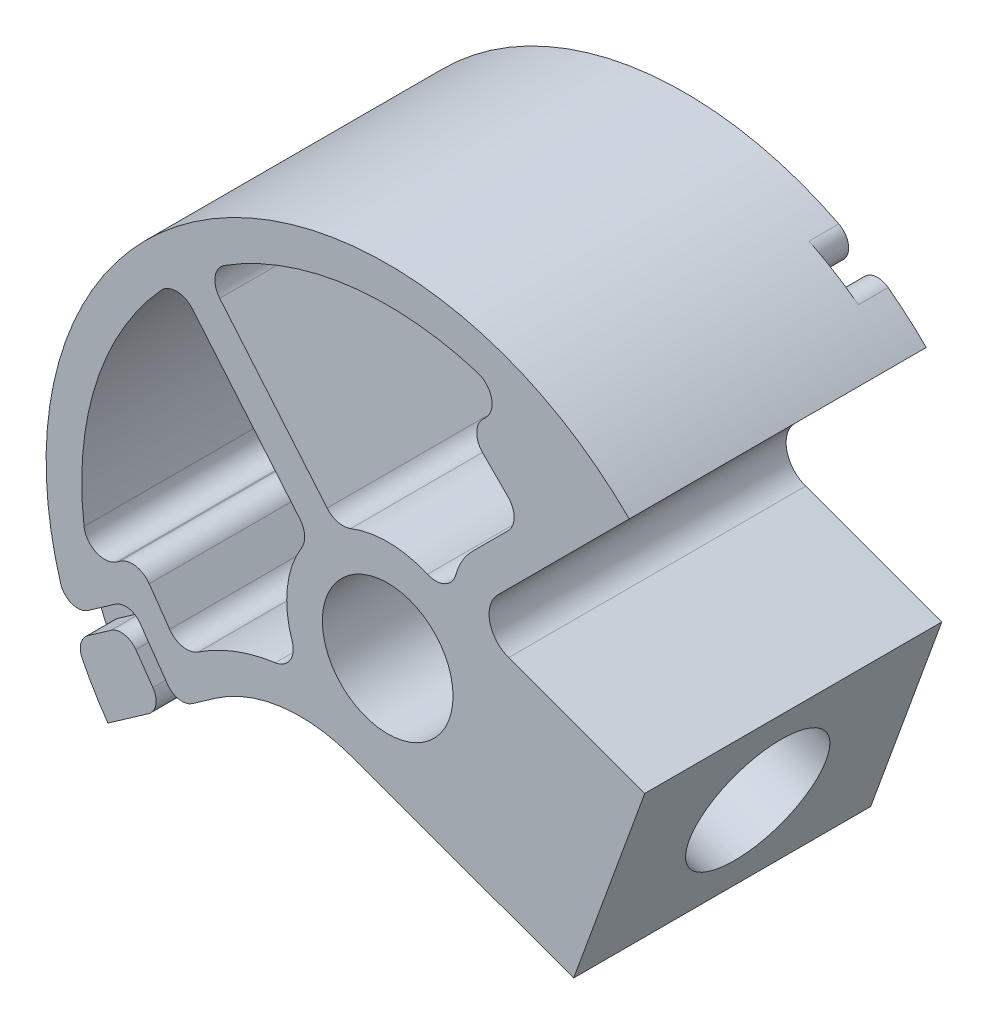
SolidWorks part; units mm, degrees
ref_plane "Front Plane" through (0, 0, 0) normal (0, 0, 1) x (1, 0, 0)
ref_plane "Top Plane" through (0, 0, 0) normal (0, 1, 0) x (1, 0, 0)
ref_plane "Right Plane" through (0, 0, 0) normal (1, 0, 0) x (0, 0, -1)
sketch "Sketch1" plane through (0, 0, 0) normal (0, 0, 1) x (1, 0, 0)
  line L0 (0, 0) -> (-47.1012, -32.9806)
  line L1 (0, 0) -> (0, 57.5) construction
  line L2 (0, 0) -> (40.6586, 40.6586)
  line L3 (-51.0007, -26.5552) -> (0, 9.1558)
  line L4 (0, 10.6066) -> (35.008, 45.6146)
  line L7 (-1.6002, 18.2902) -> (43.2789, 1.9556)
  line L8 (43.2789, 1.9556) -> (31.3082, -30.9337)
  line L9 (31.3082, -30.9337) -> (-6.2795, -17.2528)
  circle A0 centre (0, 0) radius 11
  circle A1 centre (0, 0) radius 57.5
  circle A2 centre (0, 0) radius 18.3601
  circle A3 centre (0, 0) radius 50
  point P21 (12.9826, 12.9826)
  dimension "D1" = 115
  dimension "D3" = 22
  dimension "D4" = 35
  dimension "D2" = 125
  dimension "D6" = 7.5
  dimension "D9" = 40
  dimension "D10" = 45
  dimension "D11" = 7.5
  dimension "D12" = 110
  dimension "D5" = 7.5
extrude "Boss-Extrude1" add sketch "Sketch1" along normal blind 50 contours L3 A2 L0 A0 | A0 L1 L7 A2 L3 | L1 A0 L4 L7 | L1 L7 L4 A2 | L7 A2 L4 | A0 L2 L7 L4 | L7 L1 A2 | L2 A3 L4 A2 | L1 A2 A3 | A2 L1 A3 | L0 A2 L2 A0 | L3 A3 L0 A2 | A3 L3 A1 L0 | A3 L1 A1 L3 | L1 A3 L4 A1 | A3 L2 A1 L4 | A2 L9 L8 L7 region at (3.4455, -10.9277, 0) region at (-13.6142, -4.8303, 0) region at (6.8423, 12.0586, 0) region at (-29.8667, -16.3106, 0) region at (-9.9193, 9.0285, 0) region at (21.2491, 26.5807, 0) region at (25.1288, -10.4147, 0) region at (8.6084, 15.2909, 0) region at (1.7421, 14.7251, 0) region at (-46.0395, -27.6518, 0) region at (-26.0229, 17.1513, 0) region at (35.2263, 40.5384, 0) region at (3.3663, 17.2727, 0) region at (10.6696, 35.4842, 0) region at (-48.4825, -23.5487, 0) region at (-0.5426, 18.1267, 0) region at (16.7911, 50.1911, 0)
fillet "Fillet2" radius 25 1 edges at (-15.0397, -10.5309, 25)
fillet "Fillet5" radius 5 1 edges at (12.9826, 12.9826, 25)
sketch "Sketch4" plane through (0, 0, 50) normal (0, 0, 1) x (1, 0, 0)
  line L0 (-45.3405, -24.4231) -> (-32.4621, -15.4056)
  line L1 (-4.0787, -11.6688) -> (27.7221, -23.2434)
  line L2 (27.7221, -23.2434) -> (35.5886, -1.6304)
  line L3 (35.5886, -1.6304) -> (18.3055, 4.6601)
  line L4 (14.2896, 22.7749) -> (31.9254, 40.4107)
  line L5 (43.2789, 1.9556) -> (20.3577, 10.2982)
  line L6 (18.5322, 18.5322) -> (40.6586, 40.6586)
  line L7 (-47.1012, -32.9806) -> (-29.0207, -20.3205)
  line L8 (-6.1308, -17.307) -> (31.3082, -30.9337)
  line L9 (31.3082, -30.9337) -> (43.2789, 1.9556)
  line L10 (43.2789, 1.9556) -> (20.3577, 10.2982)
  line L11 (18.5322, 18.5322) -> (40.6586, 40.6586)
  line L12 (-47.1012, -32.9806) -> (-29.0207, -20.3205)
  line L13 (-6.1308, -17.307) -> (31.3082, -30.9337)
  line L14 (31.3082, -30.9337) -> (43.2789, 1.9556)
  line L15 (-35.3455, 37.4559) -> (-9.1008, 6.1787)
  line L16 (-30.7492, 41.3127) -> (-4.5045, 10.0354)
  line L17 (0, 0) -> (-33.1036, 39.4513) construction
  line L18 (-41.2447, -21.5552) -> (-44.1126, -17.4595)
  line L19 (-43.3759, -13.2813) -> (-53.7139, -20.52)
  line L20 (-38.7873, -19.8345) -> (-43.3759, -13.2813)
  line L21 (-44.1126, -17.4595) -> (-52.5407, -23.3608)
  line L22 (-55.3535, -15.5642) -> (-42.148, -6.3176)
  line L23 (-42.148, -6.3176) -> (-34.6915, -16.9666)
  line L24 (-41.2447, -21.5552) -> (-37.8033, -26.4701)
  line L25 (-38.7873, -19.8345) -> (-35.3458, -24.7494)
  line L26 (-29.0207, -20.3205) -> (-47.1012, -32.9806) construction
  line L27 (32.1295, 47.6859) -> (24.8543, 40.4107)
  line L28 (24.8543, 40.4107) -> (32.6325, 32.6325)
  line L29 (30.5112, 30.5112) -> (20.6117, 40.4107)
  line L30 (20.6117, 40.4107) -> (29.5356, 49.3346)
  line L31 (22.733, 31.2183) -> (13.5406, 40.4107)
  line L32 (13.5406, 40.4107) -> (24.9398, 51.8098)
  line L33 (18.5322, 18.5322) -> (40.6586, 40.6586) construction
  arc A0 (31.9254, 40.4107) -> (-45.3405, -24.4231) centre (0, 0) ccw
  arc A1 (-4.0787, -11.6688) -> (-32.4621, -15.4056) centre (-14.6813, -40.7993) ccw
  arc A2 (14.2896, 22.7749) -> (18.3055, 4.6601) centre (22.0678, 14.9967) ccw
  arc A3 (18.5322, 18.5322) -> (20.3577, 10.2982) centre (22.0678, 14.9967) ccw
  arc A4 (40.6586, 40.6586) -> (-47.1012, -32.9806) centre (0, 0) ccw
  arc A5 (-6.1308, -17.307) -> (-29.0207, -20.3205) centre (-14.6813, -40.7993) ccw
  arc A6 (18.5322, 18.5322) -> (20.3577, 10.2982) centre (22.0678, 14.9967) ccw
  arc A7 (40.6586, 40.6586) -> (-47.1012, -32.9806) centre (0, 0) ccw
  arc A8 (-6.1308, -17.307) -> (-29.0207, -20.3205) centre (-14.6813, -40.7993) ccw
  circle A9 centre (0, 0) radius 11 construction
  circle A10 centre (0, 0) radius 11
  circle A11 centre (0, 0) radius 17
  arc M16 (40.6586, 40.6586) -> (-47.1012, -32.9806) centre (0, 0) ccw
  dimension "D3" = 3
  dimension "D4" = 3
  dimension "D6" = 5
  dimension "D7" = 3
  dimension "D8" = 5
  dimension "D9" = 3
  dimension "D10" = 5
  dimension "D11" = 5
  dimension "D12" = 5
  dimension "D13" = 5
  dimension "D14" = 3
  dimension "D15" = 5
  dimension "D16" = 3
  dimension "D17" = 5
  dimension "D1" = 0
  dimension "D2" = 6
  dimension "D5" = 6
extrude "Cut-Extrude2" cut sketch "Sketch4" along direction (0, 0, 1) on the side against the normal up to surface (50 mm away) from surface contours A11 L15 A0 L0 A1 | A11 A2 L4 A0 L16 region at (-33.5, 8.0332, 50) region at (-2.3568, 34.6464, 50) up to face at (4.4396, 1.5514, 0) starting at face at (4.4396, 1.5514, 50)
fillet "Fillet6" radius 3.5 12 edges at (-13.8843, -9.8096, 25) (-13.054, 10.89, 25) (-35.3455, 37.4559, 25) (-30.7492, 41.3127, 25) (-8.4578, 14.7467, 25) (11.3124, 12.6898, 25) (-50.1083, -11.8915, 25) (-34.6915, -16.9666, 25) (-42.148, -6.3176, 25) (22.733, 31.2183, 25) (13.5406, 40.4107, 25) (20.4121, 47.2821, 25)
extrude "Cut-Extrude3" cut sketch "Sketch4<3>" against normal blind 5 contours A0 L19 L21 M16 | L19 A0 L21 L18 L0 L20 | L25 L0 L24 L12 region at (-43.6625, -17.4012, 50) region at (-38.2953, -23.1523, 50) region at (-50.6146, -20.177, 50)
sketch "Sketch4<3>" plane through (0, 0, 50) normal (0, 0, 1) x (1, 0, 0) same geometry as "Sketch4"
extrude "Cut-Extrude4" cut sketch "Sketch4<4>" along normal blind 5 from surface contours A0 L27 L30 M16 | L27 A0 L30 L29 L4 L28 | L29 L11 L28 L4 region at (28.6596, 46.342, 50) region at (24.7188, 39.9775, 50) region at (29.4505, 33.6931, 50) starting at face at (-32.5887, 1.2551, 0)
sketch "Sketch4<4>" plane through (0, 0, 50) normal (0, 0, 1) x (1, 0, 0) same geometry as "Sketch4"
sketch "Sketch2" plane through (37.5877, -13.6808, 0) normal (0.9397, -0.342, 0) x (0, 0, -1)
  line L0 (-50, 16.6399) -> (0, -18.3601) construction
  line L7 (0, -18.3601) -> (0, 16.6399)
  line L8 (0, 16.6399) -> (-50, 16.6399)
  line L9 (-50, 16.6399) -> (-50, -18.3601)
  line L10 (-50, -18.3601) -> (0, -18.3601)
  line L11 (0, -18.3601) -> (0, 16.6399)
  line L12 (0, 16.6399) -> (-50, 16.6399)
  line L13 (-50, 16.6399) -> (-50, -18.3601)
  line L14 (-50, -18.3601) -> (0, -18.3601)
  circle A0 centre (-25, -0.8601) radius 11.5
  point P2 (0, -20.882)
  point P6 (-17.5, -3.8052)
  point P7 (-35, 16.6399)
  point P8 (-33.6569, 12.3735)
  point P11 (-35, 14.1215)
  dimension "D1" = 23
  dimension "D2" = 0
extrude "Cut-Extrude1" cut sketch "Sketch2" against normal blind 20 contours A0 L0 | L0 A0 region at (38.6611, -10.7317, 22.2011) region at (35.926, -18.2464, 27.7989)
fillet "Fillet8" radius 3 12 edges at (32.6325, 32.6325, 2.5) (20.6117, 40.4107, 2.5) (30.5112, 30.5112, 2.5) (24.8543, 40.4107, 2.5) (29.5356, 49.3346, 2.5) (32.1295, 47.6859, 2.5) (-52.5407, -23.3608, 47.5) (-44.1126, -17.4595, 47.5) (-53.7139, -20.52, 47.5) (-43.3759, -13.2813, 47.5) (-37.8033, -26.4701, 47.5) (-35.3458, -24.7494, 47.5)
